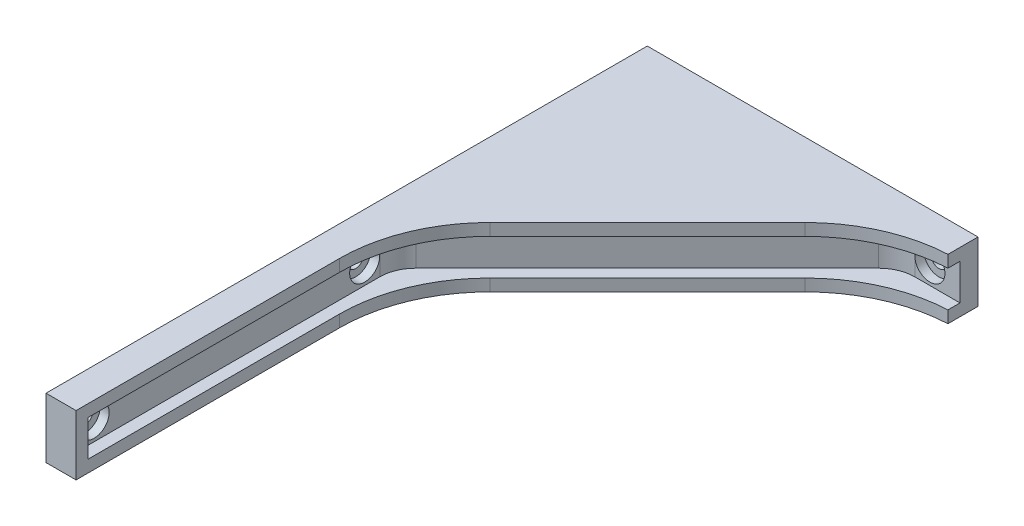
SolidWorks part; units mm, degrees
ref_plane "前视基准面" through (0, 0, 0) normal (0, 0, 1) x (1, 0, 0)
ref_plane "上视基准面" through (0, 0, 0) normal (0, 1, 0) x (1, 0, 0)
ref_plane "右视基准面" through (0, 0, 0) normal (1, 0, 0) x (0, 0, -1)
other "Configuration Table"
sketch "草图1" plane through (0, 0, 0) normal (0, 1, 0) x (1, 0, 0)
  line L0 (0, 0) -> (110, 0)
  line L1 (0, 0) -> (0, -110)
  line L2 (110, 0) -> (110, -6)
  line L3 (110, -6) -> (90, -6)
  line L4 (0, -110) -> (6, -110)
  line L5 (6, -110) -> (6, -90)
  line L6 (6, -90) -> (90, -6)
extrude "凸台-拉伸1" add sketch "草图1" along normal blind 20
sketch "草图2" plane through (6, 0, 0) normal (1, 0, 0) x (0, 0, -1)
  line L0 (-110, 20) -> (-90, 0)
  circle A0 centre (-100, 10) radius 2.6
extrude "切除-拉伸1" cut sketch "草图2" against normal blind 20 contours L0 A0 | L0 A0 region at (6, 10.7803, 99.2197) region at (6, 9.2197, 100.7803)
sketch "草图3" plane through (6, 0, 0) normal (1, 0, 0) x (0, 0, -1)
  circle A0 centre (-100, 10) radius 5
extrude "切除-拉伸2" cut sketch "草图3" against normal blind 3
sketch "草图4" plane through (0, 0, 6) normal (0, 0, 1) x (1, 0, 0)
  line L0 (90, 20) -> (110, 0)
  circle A0 centre (100, 10) radius 2.6
extrude "切除-拉伸3" cut sketch "草图4" against normal blind 6 contours L0 A0 | L0 A0 region at (100.7803, 10.7803, 6) region at (99.2197, 9.2197, 6)
sketch "草图5" plane through (0, 0, 6) normal (0, 0, 1) x (1, 0, 0)
  circle A0 centre (100, 10) radius 5
extrude "切除-拉伸4" cut sketch "草图5" against normal blind 3
sketch "草图6" plane through (0, 0, 0) normal (-1, 0, 0) x (0, 0, 1)
  line L1 (110, 0) -> (200, 0)
  line L2 (110, 0) -> (110, 20)
  line L3 (110, 20) -> (200, 20)
  line L4 (200, 0) -> (200, 20)
extrude "凸台-拉伸2" add sketch "草图6" against normal blind 6
sketch "草图7" plane through (6, 0, 0) normal (1, 0, 0) x (0, 0, -1)
  line L0 (-200, 10) -> (-190, 10)
  line L1 (-200, 0) -> (-200, 20) construction
  circle A0 centre (-190, 10) radius 5
extrude "切除-拉伸5" cut sketch "草图7" against normal blind 3 contours A0 region at (6, 5.1414, 190)
sketch "草图8" plane through (3, 0, 0) normal (1, 0, 0) x (0, 0, -1)
  circle A0 centre (-190, 10) radius 2.6
extrude "切除-拉伸6" cut sketch "草图8" against normal blind 3
sketch "草图11" plane through (48, 0, 48) normal (0.7071, 0, 0.7071) x (0.7071, 0, -0.7071)
  line L0 (-59.397, 20) -> (-59.397, 0) construction
  line L1 (59.397, 20) -> (-59.397, 20)
  line L2 (59.397, 20) -> (59.397, 16)
  line L3 (59.397, 16) -> (-59.397, 16)
  line L4 (-59.397, 20) -> (-59.397, 16)
  line L5 (59.397, 20) -> (59.397, 0) construction
  line L6 (-59.397, 0) -> (59.397, 0)
  line L7 (-59.397, 0) -> (-59.397, 4)
  line L8 (-59.397, 4) -> (59.397, 4)
  line L9 (59.397, 0) -> (59.397, 4)
extrude "凸台-拉伸4" add sketch "草图11" along normal blind 4
sketch "草图12" plane through (6, 0, 0) normal (1, 0, 0) x (0, 0, -1)
  line L1 (-200, 20) -> (-90, 20)
  line L2 (-200, 20) -> (-200, 16)
  line L3 (-200, 16) -> (-90, 16)
  line L4 (-90, 20) -> (-90, 16)
  line L5 (-200, 0) -> (-90, 0)
  line L6 (-200, 0) -> (-200, 4)
  line L7 (-200, 4) -> (-90, 4)
  line L8 (-90, 0) -> (-90, 4)
extrude "凸台-拉伸5" add sketch "草图12" along normal blind 4
sketch "草图13" plane through (0, 0, 6) normal (0, 0, 1) x (1, 0, 0)
  line L0 (90, 0) -> (110, 0) construction
  line L1 (90, 16) -> (110, 16)
  line L2 (90, 16) -> (90, 20)
  line L3 (90, 20) -> (110, 20)
  line L4 (110, 16) -> (110, 20)
  line L5 (90, 4) -> (110, 4)
  line L6 (90, 4) -> (90, 0)
  line L7 (90, 0) -> (110, 0)
  line L8 (110, 4) -> (110, 0)
extrude "凸台-拉伸6" add sketch "草图13" along normal blind 4
fillet "圆角2" radius 12 2 edges at (90, 10, 6) (6, 10, 90)
fillet "圆角3" radius 50 4 edges at (10, 2, 91.6569) (10, 18, 91.6569) (91.6569, 2, 10) (91.6569, 18, 10)
sketch "草图14" plane through (6, 0, 0) normal (1, 0, 0) x (0, 0, -1)
  line L0 (-112.3675, 4) -> (-200, 4) construction
  line L1 (-200, 16) -> (-196, 16)
  line L2 (-200, 16) -> (-200, 4)
  line L3 (-200, 4) -> (-196, 4)
  line L4 (-196, 16) -> (-196, 4)
extrude "凸台-拉伸7" add sketch "草图14" along normal blind 4
